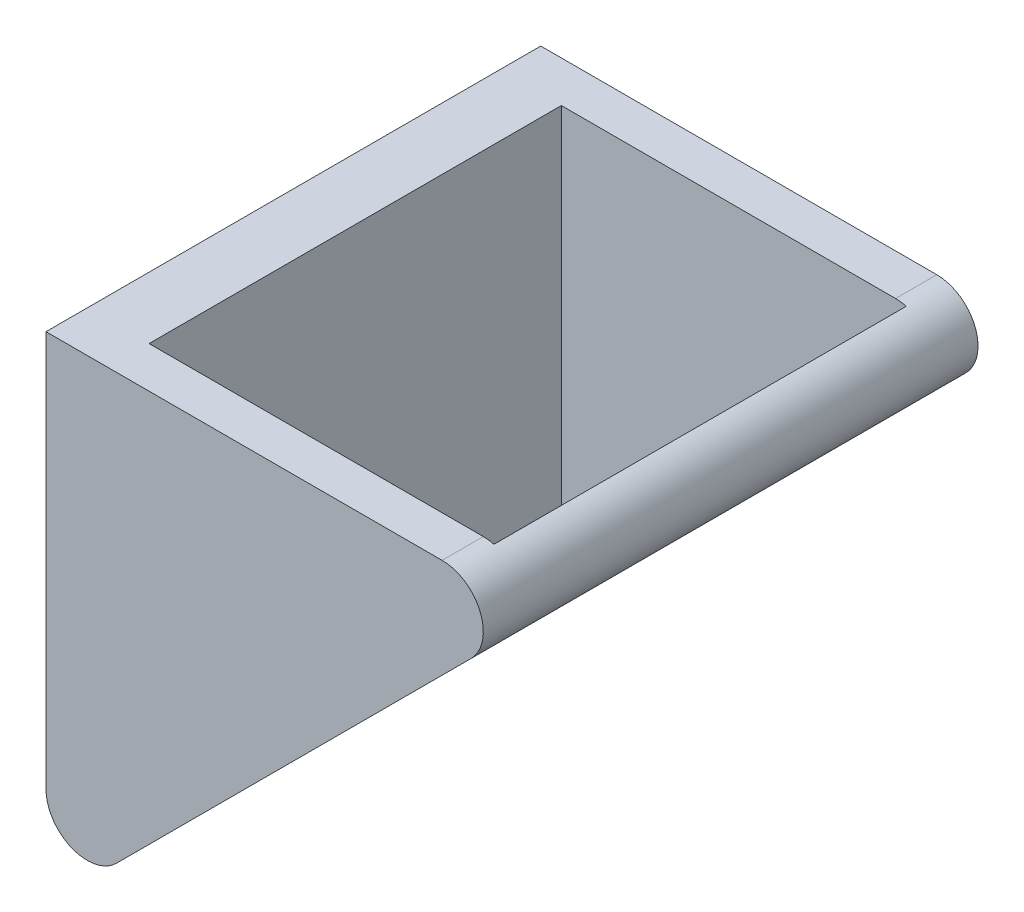
SolidWorks part; units mm, degrees
ref_plane "Front Plane" through (0, 0, 0) normal (0, 0, 1) x (1, 0, 0)
ref_plane "Top Plane" through (0, 0, 0) normal (0, 1, 0) x (1, 0, 0)
ref_plane "Right Plane" through (0, 0, 0) normal (1, 0, 0) x (0, 0, -1)
sketch "Sketch1" plane through (0, 0, 0) normal (0, 0, 1) x (1, 0, 0)
  line L0 (0, 0) -> (0, -12.0208)
  line L1 (0, -12.0208) -> (12.0208, 0)
  line L2 (12.0208, 0) -> (0, 0)
  line L3 (1.5, -1.5) -> (1.5, -8.3995)
  line L4 (1.5, -8.3995) -> (8.3995, -1.5)
  line L5 (8.3995, -1.5) -> (1.5, -1.5)
  line L6 (1.5, -1.5) -> (1.5, 0)
  line L7 (8.3995, -1.5) -> (9.8995, 0)
  dimension "D1" = 45
  dimension "D2" = 17
  dimension "D3" = 1.5
extrude "Boss-Extrude1" add sketch "Sketch1" along normal blind 12 contours L7 L4 L3 L6 L2 L0 L1 region at (0.75, -0.17, 0)
sketch "Sketch2" plane through (0, 0, 12) normal (0, 0, 1) x (1, 0, 0)
  line L0 (0, 0) -> (12.0208, 0)
  line L1 (12.0208, 0) -> (0, -12.0208)
  line L2 (0, -12.0208) -> (0, 0)
extrude "Boss-Extrude2" add sketch "Sketch2" against normal blind 1
sketch "Sketch3" plane through (0, 0, 0) normal (0, 0, -1) x (-1, 0, 0)
  line L0 (-12.0208, 0) -> (0, 0)
  line L1 (0, 0) -> (0, -12.0208)
  line L2 (0, -12.0208) -> (-12.0208, 0)
extrude "Boss-Extrude3" add sketch "Sketch3" against normal blind 1
fillet "Fillet1" radius 1 2 edges at (0, -12.0208, 6) (12.0208, 0, 6)
sketch "Sketch5" plane through (4.9497, -4.9497, 0) normal (-0.7071, 0.7071, 0) x (0, 0, 1)
  line L0 (11, -4.8787) -> (8.75, -1.7134)
  line L1 (8.75, -1.7134) -> (3.25, -1.7134)
  line L2 (8.75, -1.7134) -> (8.75, 3.7866)
  line L3 (8.75, 3.7866) -> (3.25, 3.7866)
  line L4 (3.25, -1.7134) -> (3.25, 3.7866)
  line L5 (1, 6.9518) -> (3.25, 3.7866)
  dimension "D1" = 5.5
  dimension "D2" = 5.5
extrude "Cut-Extrude1" cut sketch "Sketch5" against normal through all contours L4 L1 L2 L3 region at (5.6827, -4.2168, 6)
